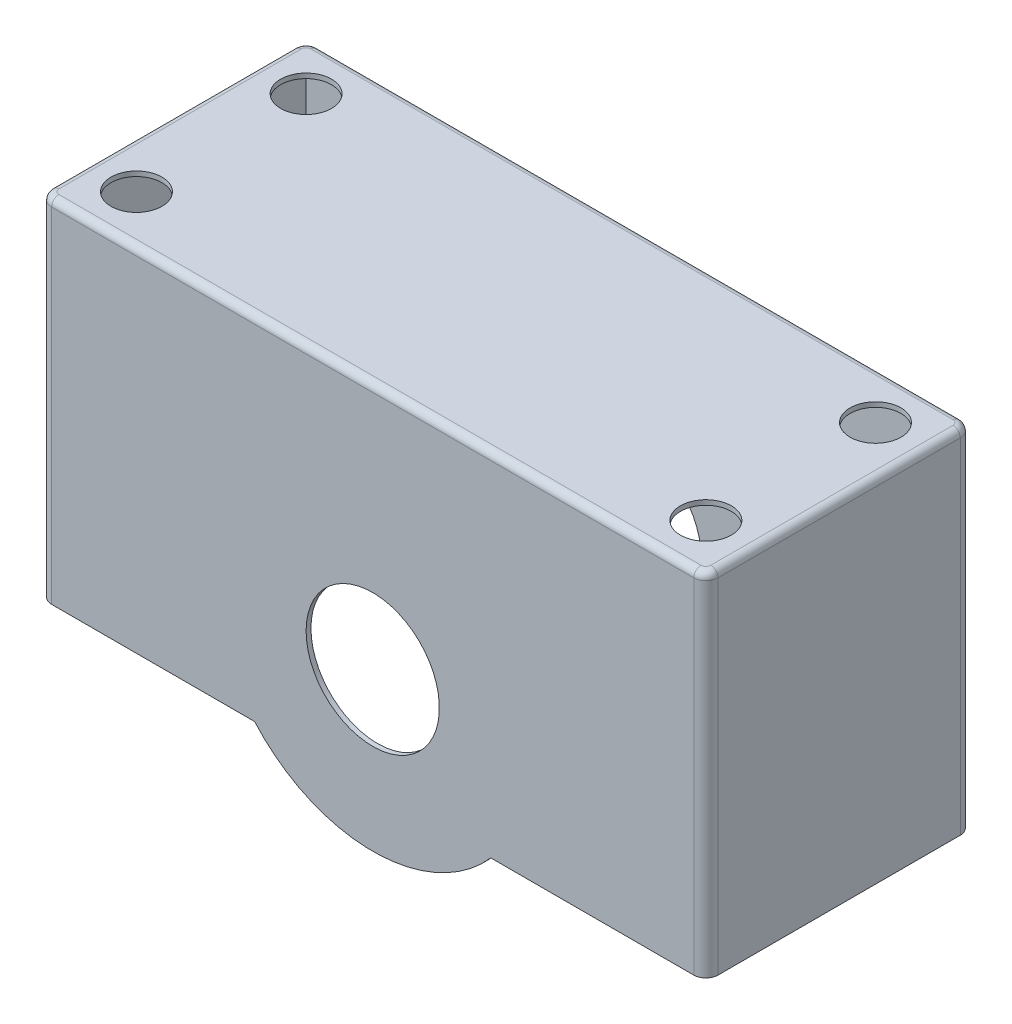
SolidWorks part; units mm, degrees
ref_plane "Plan de face" through (0, 0, 0) normal (0, 0, 1) x (1, 0, 0)
ref_plane "Plan de dessus" through (0, 0, 0) normal (0, 1, 0) x (1, 0, 0)
ref_plane "Plan de droite" through (0, 0, 0) normal (1, 0, 0) x (0, 0, -1)
sketch "Esquisse1" plane through (0, 0, 0) normal (0, 0, 1) x (1, 0, 0)
  line L0 (0, 106.6437) -> (0, 50.5) construction
  line L1 (-137.5, 72.5) -> (137.5, 72.5)
  line L2 (-137.5, 72.5) -> (-137.5, -72.5)
  line L4 (137.5, 72.5) -> (137.5, -72.5)
  line L5 (-137.5, 0) -> (137.5, 0) construction
  line L6 (-137.5, -72.5) -> (-48.7442, -72.5)
  line L7 (137.5, -72.5) -> (48.7442, -72.5)
  line L8 (0, 0) -> (0, -68.75) construction
  arc A0 (-48.7442, -72.5) -> (48.7442, -72.5) centre (0, -29.5) ccw
  point P7 (-137.5, 0)
  point P9 (0, 72.5)
  dimension "D3" = 130
  dimension "D1" = 275
  dimension "D2" = 102
  dimension "D4" = 145
extrude "Boss.-Extru.1" add sketch "Esquisse1" along normal mid plane 110
shell "Coque1" thickness 2 removed face at (-93.1221, -72.5, 0) removed face at (0, -83.5, 0) removed face at (93.1221, -72.5, 0)
ref_plane "Plan4" through (0, 0, -55) normal (0, 0, -1) x (-1, 0, 0)
sketch "Esquisse2" plane through (0, 0, -55) normal (0, 0, -1) x (-1, 0, 0)
  circle A0 centre (0, -29.5) radius 27.5
  arc A1 (-48.7442, -72.5) -> (48.7442, -72.5) centre (0, -29.5) ccw construction
  dimension "D1" = 55
extrude "Enlèv. mat.-Extru.1" cut sketch "Esquisse2" against normal through all
ref_plane "Plan5" through (0, 72.5, 0) normal (0, 1, 0) x (1, 0, 0)
sketch "Esquisse3" plane through (0, 72.5, 0) normal (0, 1, 0) x (1, 0, 0)
  line L0 (137.5, 55) -> (-137.5, 55) construction
  line L1 (-137.5, -55) -> (-137.5, 55) construction
  line L2 (137.5, -55) -> (-137.5, -55) construction
  line L3 (0, 0) -> (0, 53.6772) construction
  line L4 (91.85, 55) -> (-91.85, 55) construction
  line L5 (137.5, -55) -> (137.5, 55) construction
  circle A0 centre (-117.5, 35) radius 10.5
  circle A1 centre (-117.5, -35) radius 10.5
  circle A2 centre (117.5, 35) radius 10.5
  circle A3 centre (117.5, -35) radius 10.5
  dimension "D1" = 21
  dimension "D3" = 21
  dimension "D2" = 20
  dimension "13" = 20
  dimension "²" = 20
  dimension "D5" = 20
  dimension "137.5" = 137.5
extrude "Enlèv. mat.-Extru.2" cut sketch "Esquisse3" against normal through all
fillet "Congé2" radius 3 4 edges at (137.5, 72.5, 0) (0, 72.5, -55) (0, 72.5, 55) (-137.5, 72.5, 0)
fillet "Congé3" radius 5 8 edges at (-136.6213, 71.6213, 54.1213) (136.6213, 71.6213, 54.1213) (136.6213, 71.6213, -54.1213) (-136.6213, 71.6213, -54.1213) (-137.5, -1.5, -55) (137.5, -1.5, -55) (137.5, -1.5, 55) (-137.5, -1.5, 55)
